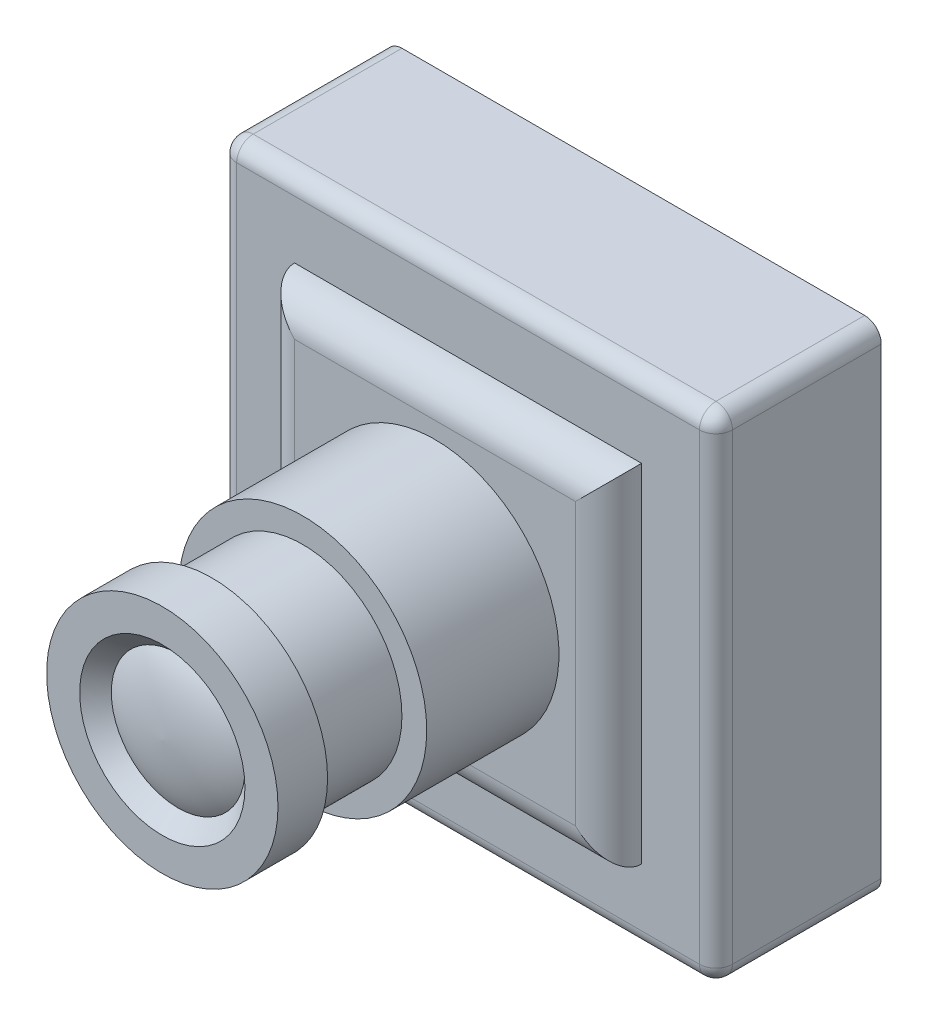
SolidWorks part; units mm, degrees
ref_plane "Front Plane" through (0, 0, 0) normal (0, 0, 1) x (1, 0, 0)
ref_plane "Top Plane" through (0, 0, 0) normal (0, 1, 0) x (1, 0, 0)
ref_plane "Right Plane" through (0, 0, 0) normal (1, 0, 0) x (0, 0, -1)
sketch "Sketch1" plane through (0, 0, 0) normal (0, 0, 1) x (1, 0, 0)
  line L0 (-15, 0) -> (0, 0) construction
  line L1 (-15, -15) -> (15, -15)
  line L2 (-15, -15) -> (-15, 15)
  line L3 (-15, 15) -> (15, 15)
  line L4 (15, -15) -> (15, 15)
  line L5 (0, 0) -> (0, 15) construction
  dimension "D1" = 30
  dimension "D2" = 30
extrude "Extrude1" add sketch "Sketch1" along normal blind 10
sketch "Sketch2" plane through (0, 0, 10) normal (0, 0, 1) x (1, 0, 0)
  line L4 (-10.5, 0) -> (0, 0) construction
  line L5 (-10.5, -10.5) -> (10.5, -10.5)
  line L6 (-10.5, -10.5) -> (-10.5, 10.5)
  line L7 (-10.5, 10.5) -> (10.5, 10.5)
  line L8 (10.5, -10.5) -> (10.5, 10.5)
  line L9 (0, -10.5) -> (0, 0) construction
  dimension "D1" = 21
  dimension "D2" = 21
extrude "Extrude2" add sketch "Sketch2" along normal blind 2
sketch "Sketch3" plane through (0, 0, 12) normal (0, 0, 1) x (1, 0, 0)
  circle A0 centre (0, 0) radius 7.5
  dimension "D1" = 15
extrude "Extrude3" add sketch "Sketch3" along normal blind 8
sketch "Sketch4" plane through (0, 0, 20) normal (0, 0, 1) x (1, 0, 0)
  circle A0 centre (0, 0) radius 6
  dimension "D1" = 12
extrude "Extrude4" add sketch "Sketch4" along normal blind 5.5
sketch "Sketch5" plane through (0, 0, 25.5) normal (0, 0, 1) x (1, 0, 0)
  circle A0 centre (0, 0) radius 7
  dimension "D1" = 14
extrude "Extrude5" add sketch "Sketch5" along normal blind 3
sketch "Sketch6" plane through (0, 0, 28.5) normal (0, 0, 1) x (1, 0, 0)
  circle A2 centre (0, 0) radius 5
  circle A3 centre (0, 0) radius 5
  dimension "D1" = 2
extrude "Cut-Extrude1" cut sketch "Sketch6" against normal blind 3
chamfer "Chamfer1" distance 3 angle 45 1 edges at (5, 0, 25.5)
ref_plane "Plane1" through (0, 0, 0) normal (1, 0, 0) x (0, 0, -1)
sketch "Sketch8" plane through (0, 0, 0) normal (1, 0, 0) x (0, 0, -1)
  line L0 (-28.5, 0) -> (-25.5, 0) construction
  line L1 (-28.5, 7) -> (-28.5, -7) construction
  line L2 (-25.5, -6) -> (-25.5, 6) construction
  line L3 (-25.5, 0) -> (-25.5, 6)
  line L4 (-28.5, 0) -> (-25.5, 0)
  spline S0 degree 3 poles (-28.5, 0) (-28.3293, 3.9624) (-27.0799, 4.8758) (-25.5, 6) knots 0 0 0 0 1 1 1 1
revolve "Revolve1" add sketch "Sketch8" angle 360 about L0
fillet "Fillet1" radius 1 8 edges at (-15, -15, 5) (-15, 15, 5) (15, 15, 5) (15, -15, 5) (15, 0, 10) (0, -15, 10) (-15, 0, 10) (0, 15, 10)
fillet "Fillet2" radius 2 4 edges at (0, -10.5, 12) (10.5, 0, 12) (0, 10.5, 12) (-10.5, 0, 12)
